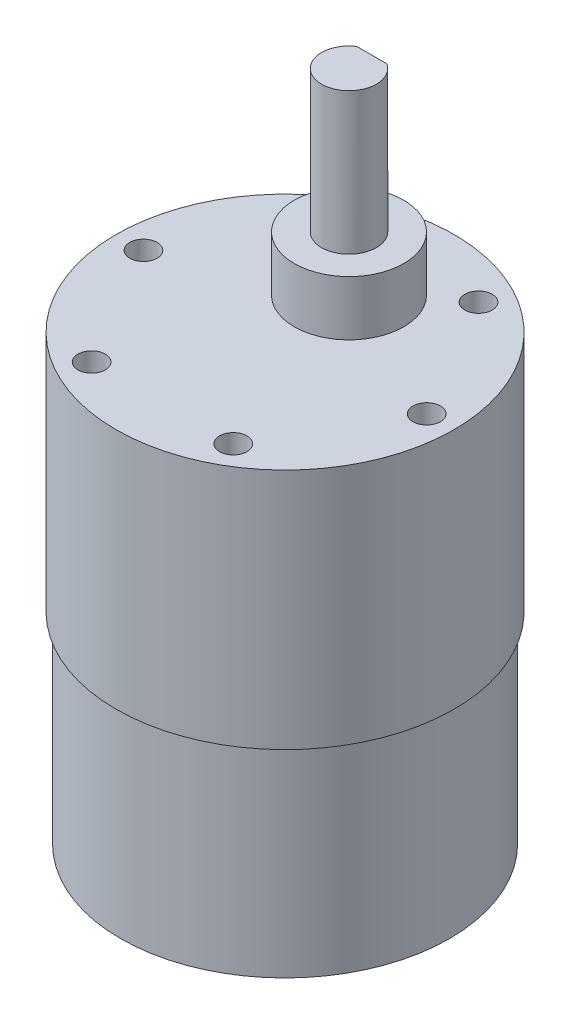
SolidWorks part; units mm, degrees
ref_plane "Front Plane" through (0, 0, 0) normal (0, 0, 1) x (1, 0, 0)
ref_plane "Top Plane" through (0, 0, 0) normal (0, 1, 0) x (1, 0, 0)
ref_plane "Right Plane" through (0, 0, 0) normal (1, 0, 0) x (0, 0, -1)
sketch "Sketch2" plane through (0, 0, 0) normal (0, 1, 0) x (1, 0, 0)
  circle A0 centre (0, 0) radius 18
  dimension "D1" = 36
extrude "Boss-Extrude1" add sketch "Sketch2" along normal blind 22
sketch "Sketch3" plane through (0, 22, 0) normal (0, 1, 0) x (1, 0, 0)
  circle A0 centre (0, 0) radius 18.5
  dimension "D1" = 37
extrude "Boss-Extrude2" add sketch "Sketch3" along normal blind 26.5
sketch "Sketch4" plane through (0, 48.5, 0) normal (0, 1, 0) x (1, 0, 0)
  circle A0 centre (-15.5, 0) radius 1.5
  dimension "D1" = 3
  dimension "D2" = 15.5
extrude "Cut-Extrude1" cut sketch "Sketch4" against normal blind 6
pattern_circular "CirPattern1" count 6 over 360 about axis through (0, 48.5, 0) along (0, 1, 0) of "Cut-Extrude1"
sketch "Sketch5" plane through (0, 48.5, 0) normal (0, 1, 0) x (1, 0, 0)
  line L0 (0, 18.5) -> (0, -18.5) construction
  circle A0 centre (0, 0) radius 18.5 construction
  circle A1 centre (0, 7) radius 6
  dimension "D1" = 12
  dimension "D2" = 7
extrude "Boss-Extrude3" add sketch "Sketch5" along normal blind 6
sketch "Sketch6" plane through (0, 54.5, 0) normal (0, 1, 0) x (1, 0, 0)
  circle A0 centre (0, 7) radius 3
  dimension "D1" = 6
extrude "Boss-Extrude4" add sketch "Sketch6" along normal blind 15.5
sketch "Sketch7" plane through (0, 70, 0) normal (0, 1, 0) x (1, 0, 0)
  line L0 (-1.6583, 9.5) -> (1.6583, 9.5)
  line L1 (0, 10) -> (0, 4) construction
  circle A0 centre (0, 7) radius 3 construction
  circle A1 centre (0, 7) radius 3 construction
  point P9 (0, 7)
  dimension "D1" = 2.5
  dimension "D2" = 3.3166
  dimension "D3" = 1.6583
extrude "Cut-Extrude2" cut sketch "Sketch7" against normal blind 12 and the other way through all
